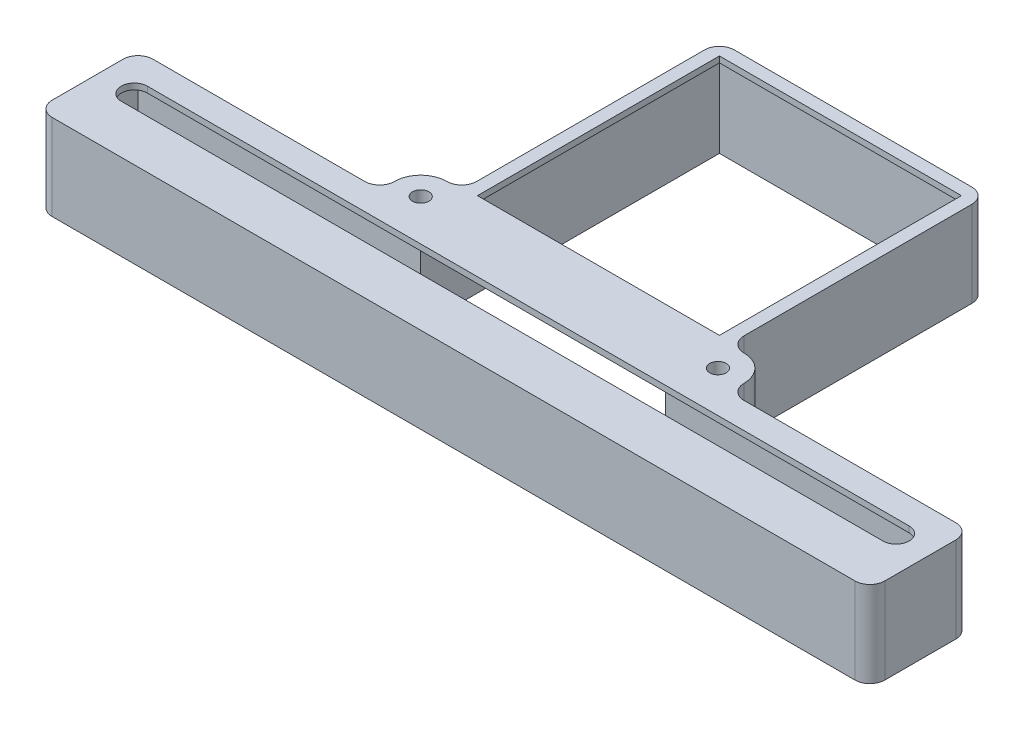
SolidWorks part; units mm, degrees
ref_plane "Front Plane" through (0, 0, 0) normal (0, 0, 1) x (1, 0, 0)
ref_plane "Top Plane" through (0, 0, 0) normal (0, 1, 0) x (1, 0, 0)
ref_plane "Right Plane" through (0, 0, 0) normal (1, 0, 0) x (0, 0, -1)
sketch "Sketch1" plane through (0, 0, 0) normal (0, 1, 0) x (1, 0, 0)
  line L0 (0, 36.3641) -> (0, -33.052) construction
  line L1 (-16.4, 25.25) -> (16.4, 25.25)
  line L2 (-16.4, 25.25) -> (-16.4, -25.25)
  line L3 (-16.4, -25.25) -> (16.4, -25.25)
  line L4 (16.4, 25.25) -> (16.4, -25.25)
  line L5 (-16.4, 25.25) -> (16.4, -25.25) construction
  line L6 (-16.4, -25.25) -> (16.4, 25.25) construction
  line L7 (-16.4, -25.25) -> (-16.4, -26.75) construction
  line L12 (-54.25, -14.75) -> (-55.75, -14.75) construction
  line L13 (-54.25, -14.75) -> (54.25, -14.75)
  line L14 (17.9, -26.75) -> (-17.9, -26.75)
  line L15 (17.9, -26.75) -> (17.9, 26.75)
  line L16 (17.9, 26.75) -> (-17.9, 26.75)
  line L17 (-17.9, -26.75) -> (-17.9, 26.75)
  line L18 (17.9, -26.75) -> (-17.9, 26.75) construction
  line L19 (17.9, 26.75) -> (-17.9, -26.75) construction
  line L20 (-16.4, 25.25) -> (-17.9, 25.25) construction
  line L21 (-16.4, 25.25) -> (-16.4, 26.75) construction
  line L22 (-54.25, -14.75) -> (-54.25, -25.25)
  line L23 (-54.25, -25.25) -> (54.25, -25.25)
  line L24 (54.25, -14.75) -> (54.25, -25.25)
  line L25 (-54.25, -14.75) -> (54.25, -25.25) construction
  line L26 (-54.25, -25.25) -> (54.25, -14.75) construction
  line L27 (-55.75, -13.25) -> (55.75, -13.25)
  line L28 (-55.75, -13.25) -> (-55.75, -26.75)
  line L29 (-55.75, -26.75) -> (55.75, -26.75)
  line L30 (55.75, -13.25) -> (55.75, -26.75)
  line L31 (-55.75, -13.25) -> (55.75, -26.75) construction
  line L32 (-55.75, -26.75) -> (55.75, -13.25) construction
  point P0 (0, 0)
  point P7 (0, -20)
  point P11 (0, -20)
  point P13 (0, 0)
  dimension "D1" = 32.8
  dimension "D2" = 50.5
  dimension "D3" = 1.5
  dimension "D4" = 108.5
  dimension "D5" = 10.5
extrude "Boss-Extrude1" add sketch "Sketch1" along normal blind 11.5 contours L17 L16 L15 L14 | L27 L30 L29 L28
sketch "Sketch2" plane through (0, 11.5, 0) normal (0, 1, 0) x (1, 0, 0)
  line L0 (0, 26.75) -> (0, -26.75) construction
  line L1 (17.9, 26.75) -> (-17.9, 26.75) construction
  line L3 (-16.2, 25.05) -> (-17.9, 25.05) construction
  line L4 (-16.2, -7.35) -> (16.2, -7.35)
  line L5 (-16.2, -7.35) -> (-16.2, 25.05)
  line L6 (-16.2, 25.05) -> (16.2, 25.05)
  line L7 (16.2, -7.35) -> (16.2, 25.05)
  line L8 (-16.2, -7.35) -> (16.2, 25.05) construction
  line L9 (-16.2, 25.05) -> (16.2, -7.35) construction
  line L10 (-17.9, -13.25) -> (-17.9, 26.75) construction
  line L11 (-16.2, 25.05) -> (-16.2, 26.75) construction
  line L12 (55.75, -26.75) -> (-55.75, -26.75) construction
  point P4 (0, 0)
  point P6 (0, 8.85)
  dimension "D1" = 32.4
extrude "Cut-Extrude1" cut sketch "Sketch2" against normal blind 8.7
sketch "Sketch3" plane through (0, 0, 0) normal (0, -1, 0) x (1, 0, 0)
  line L0 (-55.75, 20) -> (55.75, 20) construction
  line L1 (-55.75, 13.25) -> (-55.75, 26.75) construction
  line L2 (55.75, 13.25) -> (55.75, 26.75) construction
  line L3 (0, 26.75) -> (0, -26.75) construction
  line L4 (55.75, 26.75) -> (-55.75, 26.75) construction
  line L5 (17.9, -26.75) -> (-17.9, -26.75) construction
  line L6 (-54.25, 25.25) -> (-55.75, 25.25) construction
  line L7 (-54.25, 25.25) -> (54.25, 25.25)
  line L8 (-54.25, 25.25) -> (-54.25, 14.75)
  line L9 (-54.25, 14.75) -> (54.25, 14.75)
  line L10 (54.25, 25.25) -> (54.25, 14.75)
  line L11 (-54.25, 25.25) -> (54.25, 14.75) construction
  line L12 (-54.25, 14.75) -> (54.25, 25.25) construction
  line L13 (-54.25, 25.25) -> (-54.25, 26.75) construction
  point P12 (0, 20)
  dimension "D1" = 1.5
extrude "Cut-Extrude2" cut sketch "Sketch3" against normal offset from surface (10.7 mm away) 0.8 up to face at (0, 11.5, -8.85)
sketch "Sketch4" plane through (0, 10.7, 0) normal (0, -1, 0) x (1, 0, 0)
  line L0 (-54.25, 18.5) -> (54.25, 18.5) construction
  line L1 (-54.25, 14.75) -> (-54.25, 25.25) construction
  line L2 (54.25, 25.25) -> (54.25, 14.75) construction
  line L3 (54.25, 14.75) -> (-54.25, 14.75) construction
  line L4 (51, 18.5) -> (-51, 18.5) construction
  line L5 (51, 16.75) -> (-51, 16.75)
  line L6 (51, 20.25) -> (-51, 20.25)
  arc A0 (51, 16.75) -> (51, 20.25) centre (51, 18.5) ccw
  arc A1 (-51, 20.25) -> (-51, 16.75) centre (-51, 18.5) ccw
  point P10 (0, 18.5)
  dimension "D1" = 3.75
  dimension "D2" = 3.5
  dimension "D3" = 102
extrude "Cut-Extrude3" cut sketch "Sketch4" against normal up to next
sketch "Sketch5" plane through (0, 0, 0) normal (0, -1, 0) x (1, 0, 0)
  line L0 (-17.9, -6.75) -> (17.9, -6.75) construction
  line L1 (-17.9, 13.25) -> (-17.9, -26.75) construction
  line L2 (17.9, 13.25) -> (17.9, -26.75) construction
  line L3 (-17.9, 13.25) -> (17.9, 13.25) construction
  line L4 (0, -26.75) -> (0, 13.25) construction
  line L5 (17.9, -26.75) -> (-17.9, -26.75) construction
  line L7 (-16.4, 14.75) -> (16.4, 14.75)
  line L8 (-16.4, 14.75) -> (-16.4, -25.25)
  line L9 (-16.4, -25.25) -> (16.4, -25.25)
  line L10 (16.4, 14.75) -> (16.4, -25.25)
  line L11 (-16.4, 14.75) -> (16.4, -25.25) construction
  line L12 (-16.4, -25.25) -> (16.4, 14.75) construction
  line L13 (54.25, 14.75) -> (-54.25, 14.75) construction
  line L14 (16.4, -25.25) -> (17.9, -25.25) construction
  line L15 (16.4, -25.25) -> (16.4, -26.75) construction
  point P14 (0, -5.25)
  dimension "D1" = 1.5
extrude "Cut-Extrude4" cut sketch "Sketch5" against normal up to surface (10.7 mm away) up to face at (0, 10.7, 18.5)
sketch "Sketch6" plane through (0, 10.7, 0) normal (0, -1, 0) x (1, 0, 0)
  line L0 (-16.4, -25.25) -> (-16.4, 14.75) construction
  line L1 (-16.4, 7.35) -> (16.4, 7.35)
  line L2 (-16.4, 7.35) -> (-16.4, 8.85)
  line L3 (-16.4, 8.85) -> (16.4, 8.85)
  line L4 (16.4, 7.35) -> (16.4, 8.85)
  line L5 (16.4, -25.25) -> (16.4, 14.75) construction
  line L7 (-16.2, 7.35) -> (16.2, 7.35) construction
  dimension "D1" = 1.5
extrude "Boss-Extrude2" add sketch "Sketch6" along normal offset from surface (7.7 mm away) 8.5 up to face at (0, 11.5, 18.5)
sketch "Sketch8" plane through (0, 11.5, 0) normal (0, 1, 0) x (1, 0, 0)
  line L0 (-55.75, -13.25) -> (-17.9, -13.25) construction
  line L2 (0, 31.5428) -> (0, -38.2394) construction
  line L3 (-19.9, -7.75) -> (-17.9, -7.75)
  line L4 (-17.9, -13.25) -> (-17.9, 26.75) construction
  line L5 (-23.4, -11.25) -> (-23.4, -13.25)
  line L6 (23.4, -11.25) -> (23.4, -13.25)
  line L7 (19.9, -7.75) -> (17.9, -7.75)
  line L8 (-23.4, -13.25) -> (-17.9, -13.25)
  line L9 (-17.9, -13.25) -> (-17.9, -7.75)
  line L10 (17.9, -13.25) -> (17.9, -7.75)
  line L11 (23.4, -13.25) -> (17.9, -13.25)
  circle A0 centre (-19.9, -11.25) radius 2
  circle A1 centre (19.9, -11.25) radius 2
  circle A2 centre (-19.9, -11.25) radius 3.5
  circle A3 centre (19.9, -11.25) radius 3.5
  circle A4 centre (-19.9, -11.25) radius 1.1
  circle A5 centre (19.9, -11.25) radius 1.1
  line M16 (-17.9, 26.75) -> (-17.9, -13.25)
  line M17 (-17.9, -13.25) -> (-55.75, -13.25)
  line M21 (55.75, -13.25) -> (17.9, -13.25)
  line M22 (17.9, -13.25) -> (17.9, 26.75)
  dimension "D1" = 4
  dimension "D3" = 1.5
  dimension "D2" = 2.2
extrude "Boss-Extrude5" add sketch "Sketch8" against normal up to surface (11.5 mm away) contours A2 L3 M16 | L9 A2 L8 A0 | A0 A4 | A0 L9 M17 | A2 L5 M17 | L11 A1 M22 | A1 A5 | A3 L10 A1 L11 | A3 L7 M22 | L6 A3 M21 region at (-18.8752, 11.5, 7.9848) region at (-18.3906, 11.5, 7.935) region at (-23.215, 11.5, 12.7594) region at (-18.5258, 11.5, 12.6242) region at (-18.3467, 11.5, 12.8033) region at (23.1652, 11.5, 12.2748) region at (23.215, 11.5, 12.7594) region at (18.3906, 11.5, 7.935) region at (18.3467, 11.5, 12.8033) region at (18.5258, 11.5, 12.6242) up to face at (0, 0, 7.375)
sketch "Sketch7" plane through (0, 10.7, 0) normal (0, -1, 0) x (1, 0, 0)
  line L0 (54.25, 14.75) -> (54.25, 25.25) construction
  line L1 (-54.25, 25.25) -> (54.25, 25.25)
  line L2 (-54.25, 25.25) -> (-54.25, 24.25)
  line L3 (-54.25, 24.25) -> (54.25, 24.25)
  line L4 (54.25, 25.25) -> (54.25, 24.25)
  line L5 (-16.4, 14.75) -> (-16.4, 15.25)
  line L6 (-54.25, 14.75) -> (54.25, 14.75)
  line L7 (-54.25, 14.75) -> (-54.25, 15.25)
  line L8 (-54.25, 15.25) -> (54.25, 15.25)
  line L9 (54.25, 14.75) -> (54.25, 15.25)
  line L10 (16.4, 14.75) -> (16.4, 15.25)
  line M13 (16.4, 14.75) -> (54.25, 14.75)
  line M14 (54.25, 14.75) -> (54.25, 25.25)
  line M15 (54.25, 25.25) -> (-54.25, 25.25)
  line M16 (-54.25, 25.25) -> (-54.25, 14.75)
  line M17 (-54.25, 14.75) -> (-16.4, 14.75)
  dimension "D1" = 1
  dimension "D2" = 0.5
extrude "Boss-Extrude3" [suppressed] add sketch "Sketch7" along normal blind 1.3 contours L3 M16 M14 M15 | L8 L5 M16 M17 | L10 L8 M13 M14
fillet "Fillet1" radius 2 10 edges at (55.75, 5.75, 26.75) (55.75, 5.75, 13.25) (-55.75, 5.75, 26.75) (-55.75, 5.75, 13.25) (-17.9, 5.75, -26.75) (17.9, 5.75, -26.75) (-17.9, 5.75, 7.75) (-23.4, 5.75, 13.25) (23.4, 5.75, 13.25) (17.9, 5.75, 7.75)
